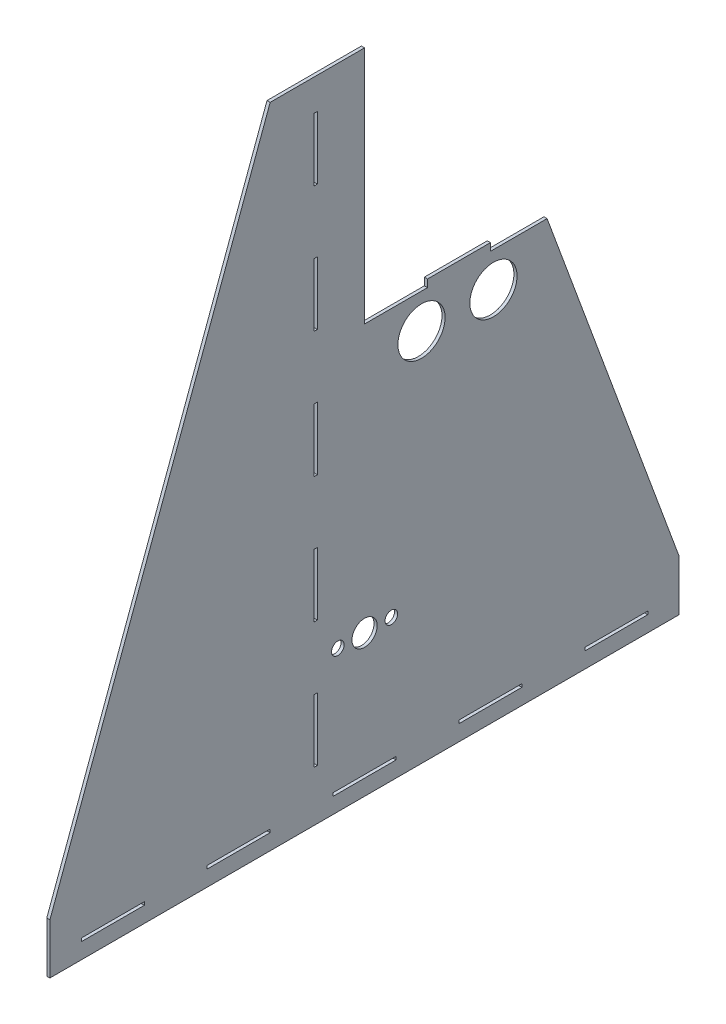
SolidWorks part; units mm, degrees
ref_plane "Přední rovina" through (0, 0, 0) normal (0, 0, 1) x (1, 0, 0)
ref_plane "Horní rovina" through (0, 0, 0) normal (0, 1, 0) x (1, 0, 0)
ref_plane "Pravá rovina" through (0, 0, 0) normal (1, 0, 0) x (0, 0, -1)
sketch "Skica1" plane through (0, 0, 0) normal (1, 0, 0) x (0, 0, -1)
  line L0 (0, 0) -> (0, 200)
  line L1 (-100, 0) -> (100, 0)
  line L2 (-100, 0) -> (-100, 206)
  line L3 (-100, 206) -> (100, 206)
  line L4 (100, 0) -> (100, 206)
  line L5 (-90, 5) -> (-70, 5)
  line L6 (-90, 5) -> (-90, 6)
  line L7 (-90, 6) -> (-70, 6)
  line L8 (-70, 5) -> (-70, 6)
  line L9 (-50, 5) -> (-30, 5)
  line L10 (-50, 5) -> (-50, 6)
  line L11 (-50, 6) -> (-30, 6)
  line L12 (-30, 5) -> (-30, 6)
  line L13 (-10, 5) -> (10, 5)
  line L14 (-10, 5) -> (-10, 6)
  line L15 (-10, 6) -> (10, 6)
  line L16 (10, 5) -> (10, 6)
  line L17 (50, 6) -> (30, 6)
  line L18 (30, 5) -> (30, 6)
  line L19 (50, 5) -> (30, 5)
  line L20 (50, 5) -> (50, 6)
  line L21 (90, 6) -> (70, 6)
  line L22 (70, 5) -> (70, 6)
  line L23 (90, 5) -> (70, 5)
  line L24 (90, 5) -> (90, 6)
  line L25 (-8.5, 45) -> (0, 45)
  line L26 (0, 200) -> (0, 206)
  line L27 (-15, 16) -> (-16, 16)
  line L28 (-15, 16) -> (-15, 36)
  line L29 (-15, 36) -> (-16, 36)
  line L30 (-16, 16) -> (-16, 36)
  line L31 (-15, 56) -> (-16, 56)
  line L32 (-15, 56) -> (-15, 76)
  line L33 (-15, 76) -> (-16, 76)
  line L34 (-16, 56) -> (-16, 76)
  line L35 (-15, 96) -> (-16, 96)
  line L36 (-15, 96) -> (-15, 116)
  line L37 (-15, 116) -> (-16, 116)
  line L38 (-16, 96) -> (-16, 116)
  line L39 (-15, 136) -> (-16, 136)
  line L40 (-15, 136) -> (-15, 156)
  line L41 (-15, 156) -> (-16, 156)
  line L42 (-16, 136) -> (-16, 156)
  line L43 (-15, 176) -> (-16, 176)
  line L44 (-15, 176) -> (-15, 196)
  line L45 (-15, 196) -> (-16, 196)
  line L46 (-16, 176) -> (-16, 196)
  line L47 (-30, 206) -> (-100, 16)
  line L48 (100, 16) -> (30, 206)
  line L49 (58, 130) -> (0, 130)
  line L51 (20, 130) -> (40, 130)
  line L52 (20, 130) -> (20, 132.3908)
  line L53 (20, 132.3908) -> (40, 132.3908)
  line L54 (40, 130) -> (40, 132.3908)
  circle A0 centre (0, 45) radius 4
  circle A1 centre (-8.5, 45) radius 2
  circle A2 centre (8.5, 45) radius 2
  circle A3 centre (18.0923, 119) radius 7.5
  circle A4 centre (40.9523, 119) radius 7.5
  point P19 (-30, 5.5)
  point P20 (-70, 5.5)
  point P21 (-80, 6)
  point P56 (-15.5, 176)
  point P57 (-30, 206)
  point P59 (30, 206)
  dimension "D13" = 8
  dimension "D15" = 4
  dimension "D31" = 15
  dimension "D33" = 6
  dimension "D1" = 200
  dimension "D2" = 100
  dimension "D3" = 206
  dimension "D4" = 20
  dimension "D5" = 10
  dimension "D6" = 20
  dimension "D7" = 20
  dimension "D8" = 20
  dimension "D9" = 20
  dimension "D10" = 1
  dimension "D11" = 5
  dimension "D12" = 0
  dimension "D14" = 8.5
  dimension "D16" = 40
  dimension "D17" = 10
  dimension "D18" = 20
  dimension "D19" = 20
  dimension "D20" = 20
  dimension "D21" = 20
  dimension "D22" = 20
  dimension "D23" = 20
  dimension "D24" = 20
  dimension "D25" = 20
  dimension "D26" = 20
  dimension "D27" = 1
  dimension "D28" = 15
  dimension "D29" = 30
  dimension "D30" = 22.86
  dimension "D32" = 74
  dimension "D34" = 20
  dimension "D35" = 20
  dimension "D36" = 73
extrude "Přidat vysunutím1" add sketch "Skica1" along normal blind 1 contours L14 L15 L0 L3 L2 L1 L13 L12 L9 L10 L11 L8 L5 L6 L7 | L16 L13 L0 L1 L4 L3 L15 L24 L23 L22 L21 L20 L19 L18 L17 | L53 L54 L51 L52 region at (0, 84.3242, 37.495) region at (0, 57.1303, -42.409)
